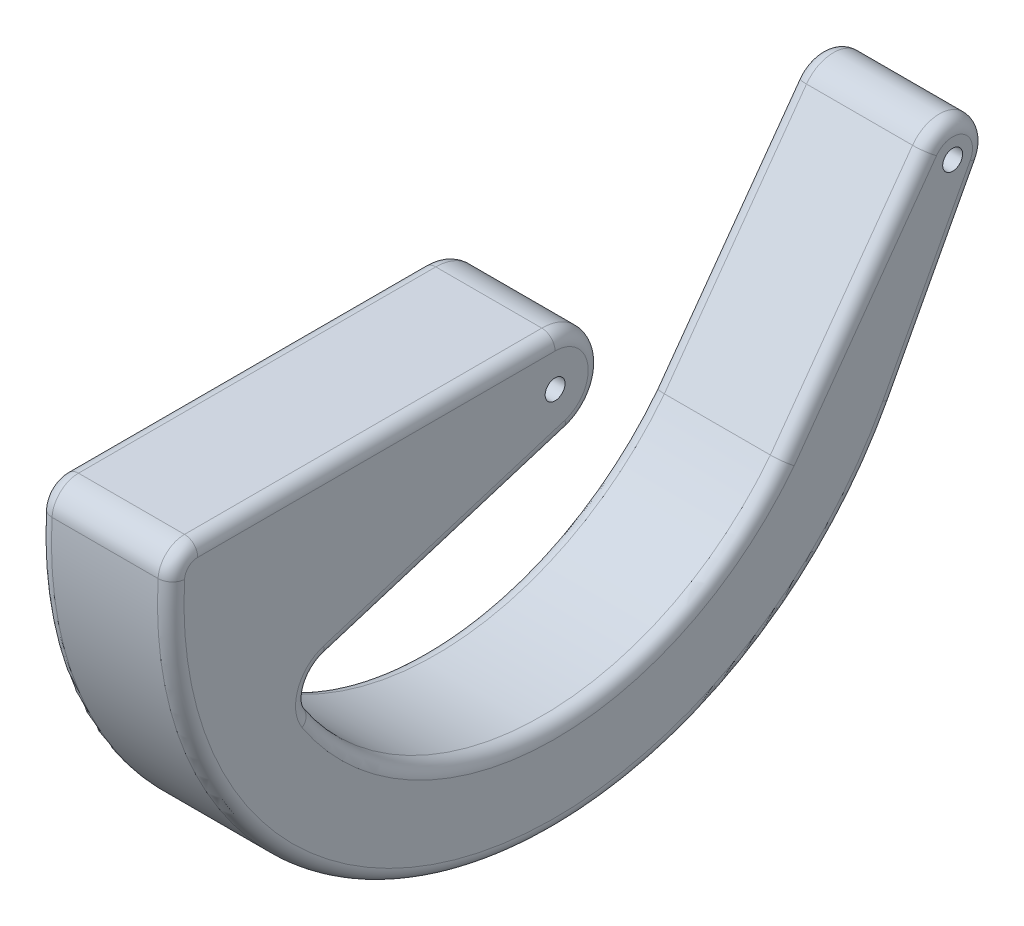
SolidWorks part; units mm, degrees
ref_plane "Front Plane" through (0, 0, 0) normal (0, 0, 1) x (1, 0, 0)
ref_plane "Top Plane" through (0, 0, 0) normal (0, 1, 0) x (1, 0, 0)
ref_plane "Right Plane" through (0, 0, 0) normal (1, 0, 0) x (0, 0, -1)
sketch "Sketch1" plane through (0, 0, 0) normal (1, 0, 0) x (0, 0, -1)
  line L0 (0, 7) -> (-53.9166, 7)
  line L1 (2.0764, -6.685) -> (-34.3524, -18)
  line L2 (55.9441, 2.924) -> (34.4918, -26.8329)
  line L3 (64.4167, -2.3437) -> (51.2333, -27.1872)
  line L6 (0, 0) -> (45.7786, -35.6134) construction
  arc A0 (0, 7) -> (2.0764, -6.685) centre (0, 0) cw
  arc A1 (-53.9166, 7) -> (-57.9104, 3.2222) centre (-53.9166, 3) ccw
  arc A2 (-57.9104, 3.2222) -> (45.7786, -35.6134) centre (0, 0) ccw
  arc A3 (-34.3524, -18) -> (-36.5076, -24.0185) centre (-33.1659, -21.82) ccw
  arc A4 (-36.5076, -24.0185) -> (34.4918, -26.8329) centre (0, 0) ccw
  circle A5 centre (0, 0) radius 1.5
  circle A6 centre (60, 0) radius 1.5
  arc A7 (55.9441, 2.924) -> (64.4167, -2.3437) centre (60, 0) cw
  circle A8 centre (0, 0) radius 60 construction
  arc A10 (45.7786, -35.6134) -> (51.2333, -27.1872) centre (0, 0) ccw
  dimension "D1" = 14.3
  dimension "D2" = 4
  dimension "D3" = 7
  dimension "D4" = 60
  dimension "D6" = 3
  dimension "D7" = 3
  dimension "D8" = 5
  dimension "D9" = 58
  dimension "D5" = 25
  dimension "D10" = 10
extrude "Extrude1" add sketch "Sketch1" along normal mid plane 20
sketch "COM" plane through (0, 0, 0) normal (1, 0, 0) x (0, 0, -1)
  line L0 (0, 0) -> (-3.1915, -23.3439) construction
  line L1 (0, 0) -> (60, 0) construction
  line L2 (60, 0) -> (-3.1915, -23.3439) construction
  dimension "D1" = 97.785
  dimension "D2" = 20.275
fillet "Fillet1" radius 2 20 edges at (10, 5.9059, 56.6653) (10, 7, 26.9583) (10, 1.0501, -6.9208) (10, -12.3425, 16.138) (10, -20.4715, 36.9318) (10, -43.6657, 1.7309) (10, -11.9544, -45.218) (10, 4.2462, -62.64) (10, -14.7655, -57.825) (10, -55.8719, 15.5669) (-10, 5.9059, 56.6653) (-10, 7, 26.9583) (-10, 1.0501, -6.9208) (-10, -12.3425, 16.138) (-10, -20.4715, 36.9318) (-10, -43.6657, 1.7309) (-10, -11.9544, -45.218) (-10, 4.2462, -62.64) (-10, -14.7655, -57.825) (-10, -55.8719, 15.5669)
